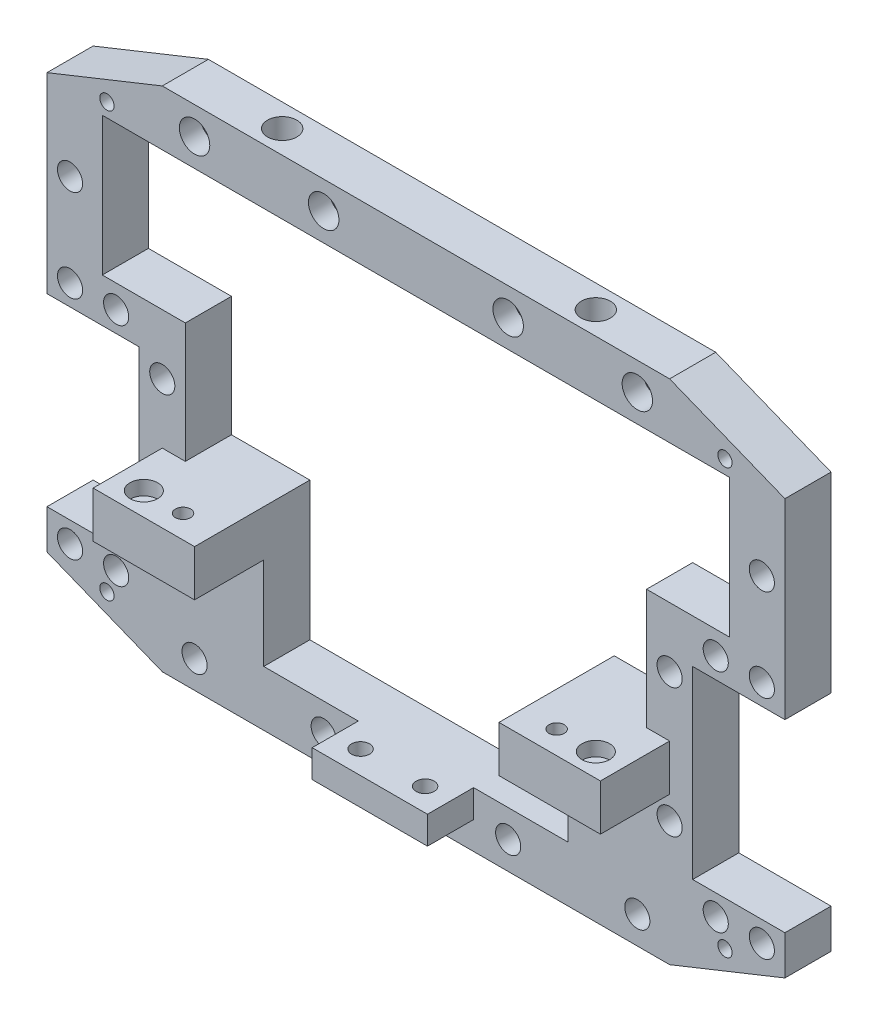
SolidWorks part; units mm, degrees
ref_plane "Ebene vorne" through (0, 0, 0) normal (0, 0, 1) x (1, 0, 0)
ref_plane "Ebene oben" through (0, 0, 0) normal (0, 1, 0) x (1, 0, 0)
ref_plane "Ebene rechts" through (0, 0, 0) normal (1, 0, 0) x (0, 0, -1)
sketch "Sketch1" plane through (0, 0, 0) normal (0, 0, 1) x (1, 0, 0)
  line L0 (6.3752, 91.162) -> (6.3752, 47.9643) construction
  line L5 (61.3752, -50.0357) -> (-48.6248, -50.0357)
  line L6 (86.3752, -40.0357) -> (86.3752, 49.9643)
  line L11 (61.3752, 59.9643) -> (-48.6248, 59.9643)
  line L12 (-73.6248, -40.0357) -> (-73.6248, 49.9643)
  line L17 (86.3752, -50.0357) -> (-73.6248, 59.9643) construction
  line L19 (86.3752, 59.9643) -> (-73.6248, -50.0357) construction
  line L20 (74.3752, -38.0357) -> (-61.6248, -38.0357)
  line L24 (74.3752, -38.0357) -> (74.3752, 47.9643)
  line L25 (74.3752, 47.9643) -> (-61.6248, 47.9643)
  line L30 (-61.6248, -38.0357) -> (-61.6248, 47.9643)
  line L43 (74.3752, -38.0357) -> (-61.6248, 47.9643) construction
  line L92 (74.3752, 47.9643) -> (-61.6248, -38.0357) construction
  line L117 (20.3752, 47.9643) -> (-7.6248, 47.9643)
  line L119 (13.3752, -38.0357) -> (-0.6248, -38.0357)
  line L121 (13.3752, 47.9643) -> (-0.6248, 47.9643)
  line L123 (13.3752, -38.0357) -> (6.3752, 4.9643) construction
  line L124 (6.3752, 4.9643) -> (-0.6248, -38.0357) construction
  line L130 (-48.6248, 59.9643) -> (-73.6248, 49.9643)
  line L131 (86.3752, 49.9643) -> (61.3752, 59.9643)
  line L132 (-48.6248, -50.0357) -> (-73.6248, -40.0357)
  line L133 (86.3752, -40.0357) -> (61.3752, -50.0357)
  line L134 (-73.6248, 4.9643) -> (85.3752, 4.9643) construction
  line L196 (-68.6248, 87.6925) -> (-68.6248, -54.0606) construction
  line L221 (6.3752, 4.9643) -> (6.3752, -91.162) construction
  circle A48 centre (-68.6248, 32.9643) radius 2.725
  circle A49 centre (-41.6248, 53.9643) radius 2.1
  circle A50 centre (-13.6248, 53.9643) radius 2.1
  circle A51 centre (26.3752, 53.9643) radius 2.1
  circle A52 centre (54.3752, 53.9643) radius 2.1
  circle A53 centre (81.3752, 32.9643) radius 2.725
  circle A54 centre (81.3752, 4.9643) radius 2.725
  circle A55 centre (81.3752, -23.0357) radius 2.725
  circle A56 centre (54.3752, -44.0357) radius 2.725
  circle A57 centre (26.3752, -44.0357) radius 2.725
  circle A58 centre (-13.6248, -44.0357) radius 2.725
  circle A59 centre (-41.6248, -44.0357) radius 2.725
  circle A60 centre (-68.6248, -23.0357) radius 2.725
  circle A61 centre (-68.6248, 4.9643) radius 2.725
  point P0 (6.3752, 4.9643)
  point P5 (6.3752, 4.9643)
  point P12 (6.3752, 4.9643)
  point P15 (6.3752, 47.9643)
  point P21 (-68.6248, 32.9643)
  point P22 (-41.6248, 53.9643)
  point P23 (-13.6248, 53.9643)
  point P24 (26.3752, 53.9643)
  point P26 (54.3752, 53.9643)
  point P27 (81.3752, 32.9643)
  point P28 (81.3752, 4.9643)
  point P29 (81.3752, -23.0357)
  point P33 (54.3752, -44.0357)
  point P34 (26.3752, -44.0357)
  point P35 (-13.6248, -44.0357)
  point P36 (-41.6248, -44.0357)
  point P62 (6.3752, 53.9643)
  point P162 (-68.6248, -23.0357)
  point P163 (-68.6248, 4.9643)
  dimension "D1" = 5.45
  dimension "D5" = 4.2
  dimension "D6" = 4.2
  dimension "D2" = 5
  dimension "D3" = 6
  dimension "D4" = 6
extrude "Boss-Extrude2" add sketch "Sketch1" along normal blind 202.6 contours L133 L6 L131 L11 L130 L12 L132 L5 A61 A60 A59 A58 A57 A56 A55 A54 A53 A52 A51 A50 A49 A48 L20 L30 L25 L117 L24 region at (6.3752, -48.0941, 0)
sketch "Sketch2" plane through (-73.6248, 0, 0) normal (-1, 0, 0) x (0, 0, 1)
  line L0 (0, 49.9643) -> (202.6, -40.0357) construction
  line L1 (202.6, -40.0357) -> (202.6, 49.9643) construction
  line L2 (10, -38.0357) -> (192.6, -38.0357)
  line L3 (10, -38.0357) -> (10, 47.9643)
  line L4 (10, 47.9643) -> (192.6, 47.9643)
  line L5 (192.6, -38.0357) -> (192.6, 47.9643)
  line L6 (10, -38.0357) -> (192.6, 47.9643) construction
  line L7 (10, 47.9643) -> (192.6, -38.0357) construction
  line L8 (202.6, 49.9643) -> (0, 49.9643) construction
  point P4 (101.3, 4.9643)
  dimension "D1" = 10
  dimension "D2" = 2
sketch "Sketch3" plane through (0, 59.9643, 0) normal (0, 1, 0) x (1, 0, 0)
  line L0 (-48.6248, 0) -> (61.3752, -202.6) construction
  line L1 (61.3752, 0) -> (-48.6248, 0) construction
  line L2 (61.3752, -192.6) -> (-48.6248, -192.6)
  line L3 (61.3752, -192.6) -> (61.3752, -10)
  line L4 (61.3752, -10) -> (-48.6248, -10)
  line L5 (-48.6248, -192.6) -> (-48.6248, -10)
  line L6 (61.3752, -192.6) -> (-48.6248, -10) construction
  line L7 (61.3752, -10) -> (-48.6248, -192.6) construction
  line L8 (61.3752, -202.6) -> (61.3752, 0) construction
  point P4 (6.3752, -101.3)
  dimension "D1" = 10
  dimension "D2" = 0
extrude "Cut-Extrude1" cut sketch "Sketch2" against normal through all
sketch "Sketch4" plane through (0, 0, 10) normal (0, 0, 1) x (1, 0, 0)
  circle A0 centre (-68.6248, 32.9643) radius 3
  circle A1 centre (-68.6248, 4.9643) radius 3
  circle A2 centre (-68.6248, -23.0357) radius 3
  circle A3 centre (-41.6248, 53.9643) radius 3
  circle A4 centre (-13.6248, 53.9643) radius 3
  circle A5 centre (26.3752, 53.9643) radius 3
  circle A6 centre (54.3752, 53.9643) radius 3
  circle A7 centre (81.3752, 32.9643) radius 3
  circle A8 centre (81.3752, 4.9643) radius 3
  circle A9 centre (81.3752, -23.0357) radius 3
  circle A10 centre (54.3752, -44.0357) radius 3
  circle A11 centre (26.3752, -44.0357) radius 3
  circle A12 centre (-13.6248, -44.0357) radius 3
  circle A13 centre (-41.6248, -44.0357) radius 3
  dimension "D1" = 6
extrude "Cut-Extrude3" cut sketch "Sketch4" along normal blind 4.5 from surface starting at face at (-65.8998, 32.9643, 192.6)
extrude "Cut-Extrude4" cut sketch "Sketch3" against normal through all
sketch "Sketch5" plane through (0, -38.0357, 0) normal (0, 1, 0) x (1, 0, 0)
  line L0 (-48.6248, -10) -> (61.3752, -192.6) construction
  line L1 (61.3752, -10) -> (-48.6248, -10) construction
  line L2 (-56.1248, -192.6) -> (68.8752, -192.6)
  line L3 (-56.1248, -192.6) -> (-56.1248, -10)
  line L4 (-56.1248, -10) -> (68.8752, -10)
  line L5 (68.8752, -192.6) -> (68.8752, -10)
  line L6 (-56.1248, -192.6) -> (68.8752, -10) construction
  line L7 (-56.1248, -10) -> (68.8752, -192.6) construction
  point P4 (6.3752, -101.3)
  dimension "D1" = 125
extrude "Cut-Extrude5" cut sketch "Sketch5" along normal through all from surface starting at face at (6.3752, -50.0357, 197.6)
sketch "Sketch6" plane through (86.3752, 0, 0) normal (1, 0, 0) x (0, 0, -1)
  line L0 (-202.6, -38.0357) -> (-202.6, -31.5357) construction
  line L1 (-202.6, -40.0357) -> (-202.6, 49.9643) construction
  line L2 (-101.3, 56.9643) -> (-101.3, -47.0357) construction
  line L3 (-202.6, -31.5357) -> (-182.6, -31.5357)
  line L4 (-202.6, -31.5357) -> (-202.6, 8.4643)
  line L5 (-202.6, 8.4643) -> (-182.6, 8.4643)
  line L6 (-182.6, -31.5357) -> (-182.6, 8.4643)
  line L7 (-10, 56.9643) -> (-192.6, 56.9643) construction
  line L8 (-10, -47.0357) -> (-192.6, -47.0357) construction
  line L9 (0, -31.5357) -> (-20, -31.5357)
  line L10 (-20, -31.5357) -> (-20, 8.4643)
  line L11 (0, -31.5357) -> (0, 8.4643)
  line L12 (0, 8.4643) -> (-20, 8.4643)
  dimension "D1" = 6.5
  dimension "D2" = 40
  dimension "D3" = 20
extrude "Cut-Extrude7" cut sketch "Sketch6" against normal up to next
sketch "Sketch8" plane through (0, 0, 202.6) normal (0, 0, 1) x (1, 0, 0)
  line L0 (86.3752, -31.5357) -> (66.3752, -31.5357) construction
  line L1 (86.3752, 8.4643) -> (66.3752, 8.4643) construction
  line L2 (66.3752, 8.4643) -> (66.3752, -31.5357)
  line L3 (66.3752, -31.5357) -> (74.3752, -31.5357)
  line L4 (74.3752, -31.5357) -> (74.3752, -38.0357)
  line L5 (74.3752, -38.0357) -> (56.3752, -38.0357)
  line L6 (74.3752, -38.0357) -> (-61.6248, -38.0357) construction
  line L7 (56.3752, -38.0357) -> (56.3752, 17.9643)
  line L8 (56.3752, 17.9643) -> (74.3752, 17.9643)
  line L9 (74.3752, 8.4643) -> (74.3752, 47.9643) construction
  line L10 (66.3752, 8.4643) -> (74.3752, 8.4643)
  line L11 (74.3752, 8.4643) -> (74.3752, 17.9643)
  line L12 (61.3752, -38.0357) -> (61.3752, 17.9643) construction
  line L13 (-68.6248, 4.9643) -> (61.3752, 4.9643) construction
  line L14 (-68.6248, -23.0357) -> (61.3752, -23.0357) construction
  circle A0 centre (61.3752, 4.9643) radius 2.725
  circle A1 centre (61.3752, -23.0357) radius 2.725
  dimension "D4" = 5.45
  dimension "D1" = 20
  dimension "D2" = 18
  dimension "D3" = 5
  dimension "D5" = 9.5
extrude "Boss-Extrude3" add sketch "Sketch8" against normal up to surface (10 mm away) up to face at (84.3752, 32.9643, 192.6)
ref_plane "Plane1" through (6.3752, 0, 0) normal (1, 0, 0) x (0, 0, -1)
extrude "Boss-Extrude4" add sketch "Sketch8<2>" against normal up to surface (202.6 mm away) from surface up to face at (-65.8998, 4.9643, 0) starting at face at (78.6502, 32.9643, 10)
sketch "Sketch8<2>" plane through (0, 0, 202.6) normal (0, 0, 1) x (1, 0, 0) same geometry as "Sketch8"
mirror "Mirror1" about plane through (6.3752, 0, 0) normal (1, 0, 0) of "Boss-Extrude4", "Boss-Extrude3", "Cut-Extrude7"
sketch "Sketch9" plane through (0, -38.0357, 0) normal (0, 1, 0) x (1, 0, 0)
  line L0 (-73.6248, -20) -> (86.3752, -20) construction
  line L1 (-73.6248, -10) -> (-73.6248, -192.6) construction
  line L2 (86.3752, -10) -> (86.3752, -192.6) construction
  line L3 (-43.6248, -10) -> (56.3752, -10) construction
  line L4 (-56.1248, -192.6) -> (-56.1248, -10) construction
  line L5 (-26.6248, -25) -> (-41.6248, -25)
  line L6 (-26.6248, -25) -> (-26.6248, -15)
  line L7 (-26.6248, -15) -> (-41.6248, -15) construction
  line L8 (-41.6248, -25) -> (-41.6248, -15)
  line L9 (-26.6248, -25) -> (-41.6248, -15) construction
  line L10 (-26.6248, -15) -> (-41.6248, -25) construction
  line L11 (-41.6248, -15) -> (-26.6248, -15)
  line L12 (-41.6248, -15) -> (-41.6248, 0)
  line L13 (-41.6248, 0) -> (-26.6248, 0)
  line L14 (-26.6248, -15) -> (-26.6248, 0)
  line L16 (-48.6248, 0) -> (-41.6248, 0)
  line L17 (-48.6248, 0) -> (-48.6248, -25)
  line L18 (-48.6248, -25) -> (-41.6248, -25)
  line L19 (-41.6248, 0) -> (-41.6248, -25)
  circle A0 centre (-34.1248, -20) radius 1.65
  point P8 (-34.1248, -20)
  line M6 (56.3752, 0) -> (-43.6248, 0)
  line M7 (-43.6248, 0) -> (-43.6248, -10)
  line M8 (-43.6248, -10) -> (56.3752, -10)
  dimension "D5" = 3.3
  dimension "D1" = 10
  dimension "D2" = 22
  dimension "D3" = 15
  dimension "D4" = 10
  dimension "D6" = 10
extrude "Boss-Extrude5" add sketch "Sketch9" against normal blind 10 from offset 30 contours L17 L18 L8 L12 L16 M8 M7 | L12 M8 M6 M7 | L14 L12 M8 M6 | L11 L14 L12 M8 | L11 L8 L5 L6 A0 region at (-34.1248, -38.0357, 24.8197) region at (-45.4474, -38.0357, 13.4677) region at (-34.1248, -38.0357, 12.5) region at (-34.1248, -38.0357, 5) region at (-42.6248, -38.0357, 5)
sketch "Sketch10" plane through (0, -18.0357, 0) normal (0, -1, 0) x (1, 0, 0)
  line L1 (-26.6248, 0) -> (-48.6248, 0)
  line L2 (-26.6248, 0) -> (-26.6248, 10)
  line L3 (-26.6248, 10) -> (-48.6248, 10)
  line L4 (-48.6248, 0) -> (-48.6248, 10)
extrude "Boss-Extrude6" add sketch "Sketch10" along normal blind 20
ref_plane "Plane2" through (0, 0, 101.3) normal (0, 0, 1) x (1, 0, 0)
mirror "Mirror2" about plane through (0, 0, 101.3) normal (0, 0, 1) of "Boss-Extrude6", "Boss-Extrude5"
mirror "Mirror3" about plane through (6.3752, 0, 0) normal (1, 0, 0) of "Boss-Extrude5", "Boss-Extrude6", "Mirror2"
sketch "Sketch11" plane through (0, 0, 202.6) normal (0, 0, 1) x (1, 0, 0)
  line L0 (-48.6248, -25.7607) -> (-48.6248, -20.3107) construction
  line L1 (61.3752, -25.7607) -> (61.3752, -20.3107) construction
  circle A0 centre (-48.6248, -23.0357) radius 2.25
  circle A1 centre (61.3752, -23.0357) radius 2.25
extrude "Cut-Extrude8" cut sketch "Sketch11" against normal through all
sketch "Sketch12" plane through (0, -8.0357, 0) normal (0, 1, 0) x (1, 0, 0)
  line L0 (-48.6248, -20) -> (61.3752, -20) construction
  line L1 (-48.6248, -10) -> (-48.6248, -25) construction
  line L2 (61.3752, -10) -> (61.3752, -25) construction
  line L3 (61.3752, -10) -> (-48.6248, -10) construction
  line L4 (-73.6248, -101.3) -> (86.3752, -101.3) construction
  line L5 (-73.6248, -202.6) -> (-73.6248, 0) construction
  line L6 (86.3752, -202.6) -> (86.3752, 0) construction
  circle A2 centre (-42.6248, -20) radius 3
  circle A3 centre (55.3752, -20) radius 3
  circle A4 centre (46.8752, -20) radius 1.65 construction
  circle A5 centre (-34.1248, -20) radius 1.65 construction
  circle A6 centre (55.3752, -182.6) radius 3
  circle A7 centre (-42.6248, -182.6) radius 3
  dimension "D2" = 6
  dimension "D3" = 6
  dimension "D5" = 8.5
  dimension "D4" = 8.5
  dimension "D1" = 10
extrude "Cut-Extrude9" cut sketch "Sketch12" against normal blind 3.1
sketch "Sketch13" plane through (0, 59.9643, 0) normal (0, 1, 0) x (1, 0, 0)
  line L0 (-52.3748, -10) -> (-52.3748, -41.4596)
  line L1 (-56.1248, -10) -> (-48.6248, -10) construction
  line L2 (-52.3748, -41.4596) -> (65.444, -41.4596)
  line L3 (65.444, -41.4596) -> (65.1252, -10)
  line L4 (61.3752, -10) -> (68.8752, -10) construction
  line L5 (65.1252, -10) -> (86.3752, -10)
  line L6 (86.3752, -10) -> (86.3752, -202.6)
  line L7 (86.3752, -202.6) -> (-73.6248, -202.6)
  line L8 (-73.6248, -202.6) -> (-73.6248, -10)
  line L9 (-73.6248, -10) -> (-52.3748, -10)
extrude "Cut-Extrude10" cut sketch "Sketch13" against normal through all
sketch "Sketch14" plane through (0, 0, 10) normal (0, 0, 1) x (1, 0, 0)
  line L0 (-73.6248, 49.9643) -> (-73.6248, 8.4643) construction
  line L1 (-61.6248, 47.9643) -> (74.3752, 47.9643) construction
  line L2 (6.3752, 59.9643) -> (6.3752, -50.0357) construction
  line L3 (61.3752, 59.9643) -> (-48.6248, 59.9643) construction
  line L4 (61.3752, -50.0357) -> (-48.6248, -50.0357) construction
  line L5 (6.3752, 4.9643) -> (89.0758, 4.9643) construction
  circle A0 centre (-60.6248, 50.9643) radius 1.55
  circle A1 centre (73.3752, 50.9643) radius 1.55
  circle A2 centre (73.3752, -41.0357) radius 1.55
  circle A3 centre (-60.6248, -41.0357) radius 1.55
  dimension "D1" = 3.1
  dimension "D2" = 13
  dimension "D3" = 3
extrude "Cut-Extrude11" cut sketch "Sketch14" against normal blind 10
sketch "Sketch15" plane through (0, 0, 0) normal (0, 0, -1) x (-1, 0, 0)
  circle A0 centre (-73.3752, 50.9643) radius 2.6
  circle A1 centre (-73.3752, -41.0357) radius 2.6
  circle A2 centre (60.6248, -41.0357) radius 2.6
  circle A3 centre (60.6248, 50.9643) radius 2.6
  dimension "D1" = 5.2
extrude "Cut-Extrude12" cut sketch "Sketch15" against normal blind 5
sketch "Sketch16" plane through (0, -50.0357, 0) normal (0, -1, 0) x (1, 0, 0)
  line L0 (6.3752, 10) -> (6.3752, 20) construction
  line L1 (61.3752, 10) -> (-48.6248, 10) construction
  line L2 (-6.1248, 15) -> (18.8752, 15) construction
  line L3 (-6.1248, 20) -> (18.8752, 20)
  line L4 (-6.1248, 20) -> (-6.1248, 10)
  line L5 (-6.1248, 10) -> (18.8752, 10)
  line L6 (18.8752, 20) -> (18.8752, 10)
  line L7 (-6.1248, 20) -> (18.8752, 10) construction
  line L8 (-6.1248, 10) -> (18.8752, 20) construction
  circle A0 centre (-0.6248, 15) radius 1.95
  circle A1 centre (13.3752, 15) radius 1.95
  point P4 (6.3752, 15)
  dimension "D3" = 3.9
  dimension "D4" = 3.9
  dimension "D1" = 10
  dimension "D2" = 25
  dimension "D5" = 7
  dimension "D6" = 7
extrude "Boss-Extrude7" add sketch "Sketch16" along normal blind 6 from offset 12 offset against normal yes
sketch "Sketch17" plane through (0, -18.0357, 0) normal (0, -1, 0) x (1, 0, 0)
  line L0 (-0.6248, 15) -> (68.4204, 15) construction
  line L1 (-0.6248, 15) -> (-58.4445, 15) construction
  line L2 (-48.6248, 10) -> (-48.6248, 25) construction
  line L3 (61.3752, 10) -> (61.3752, 25) construction
  circle A0 centre (-42.6248, 15) radius 1.95
  circle A1 centre (45.3752, 15) radius 1.95
  circle A2 centre (55.3752, 15) radius 1.95
  circle A3 centre (-32.6248, 15) radius 1.95
  circle A4 centre (13.3752, 15) radius 1.95 construction
  dimension "D1" = 10
  dimension "D2" = 10
  dimension "D3" = 6
  dimension "D4" = 6
extrude "Cut-Extrude13" cut sketch "Sketch17" against normal blind 5
sketch "Sketch18" plane through (0, 0, 10) normal (0, 0, 1) x (1, 0, 0)
  line L0 (-73.6248, 12.9643) -> (64.7633, 12.9643) construction
  line L1 (-73.6248, 49.9643) -> (-73.6248, 8.4643) construction
  line L3 (-43.6248, 17.9643) -> (-61.6248, 17.9643) construction
  circle A0 centre (-68.6248, 12.9643) radius 2.725
  circle A1 centre (-58.6248, 12.9643) radius 2.725
  circle A2 centre (-68.6248, -36.0357) radius 2.725
  circle A3 centre (-58.6248, -36.0357) radius 2.725
  dimension "D3" = 5.45
  dimension "D4" = 5
  dimension "D1" = 10
  dimension "D2" = 5
  dimension "D5" = 2
extrude "Cut-Extrude14" cut sketch "Sketch18" against normal through all
ref_plane "Plane3" through (6.3752, 59.9643, 0) normal (-1, 0, 0) x (0, 0, 1)
mirror "Mirror5" about plane through (6.3752, 59.9643, 0) normal (-1, 0, 0) of "Cut-Extrude14"
sketch "Sketch19" plane through (0, 59.9643, 0) normal (0, 1, 0) x (1, 0, 0)
  line L0 (-73.6248, -5) -> (86.3752, -5) construction
  line L1 (-73.6248, -10) -> (-73.6248, 0) construction
  line L2 (86.3752, -10) -> (86.3752, 0) construction
  circle A0 centre (-27.6248, -5) radius 3.175
  circle A1 centre (40.3752, -5) radius 3.175
  point P10 (6.3752, -5)
  dimension "D1" = 6.35
  dimension "D2" = 34
  dimension "D3" = 34
extrude "Cut-Extrude15" cut sketch "Sketch19" against normal blind 20
sketch "Sketch20" plane through (0, 0, 10) normal (0, 0, 1) x (1, 0, 0)
  circle A0 centre (-48.6248, -23.0357) radius 2.725
  circle A1 centre (61.3752, -23.0357) radius 2.725
extrude "Cut-Extrude16" cut sketch "Sketch20" against normal blind 20
sketch "Sketch21" plane through (0, 0, 10) normal (0, 0, 1) x (1, 0, 0)
  circle A0 centre (-13.6248, 53.9643) radius 3.3
  circle A1 centre (-41.6248, 53.9643) radius 3.3
  circle A2 centre (26.3752, 53.9643) radius 3.3
  circle A3 centre (54.3752, 53.9643) radius 3.3
  dimension "D1" = 6.6
extrude "Cut-Extrude17" cut sketch "Sketch21" against normal blind 4.5
